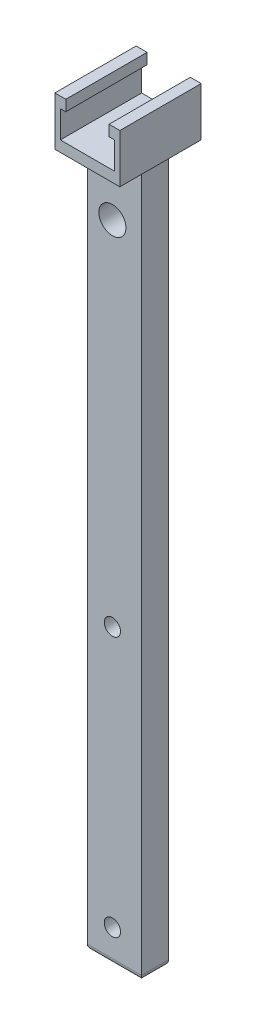
SolidWorks part; units mm, degrees
ref_plane "Front Plane" through (0, 0, 0) normal (0, 0, 1) x (1, 0, 0)
ref_plane "Top Plane" through (0, 0, 0) normal (0, 1, 0) x (1, 0, 0)
ref_plane "Right Plane" through (0, 0, 0) normal (1, 0, 0) x (0, 0, -1)
sketch "Sketch1" plane through (0, 0, 0) normal (0, 0, 1) x (1, 0, 0)
  line L0 (-5.6189, 9) -> (-5.6189, 0)
  line L1 (-5.6189, 0) -> (6.3811, 0)
  line L2 (6.3811, 0) -> (6.3811, 9)
  line L3 (4.3811, 9) -> (4.3811, 7)
  line L4 (4.3811, 7) -> (5.3991, 7)
  line L5 (5.3991, 7) -> (5.3991, 2)
  line L6 (5.3991, 2) -> (-4.6009, 2)
  line L7 (-4.6009, 2) -> (-4.6009, 7)
  line L8 (-4.6009, 7) -> (-3.6009, 7)
  line L9 (-3.6009, 7) -> (-3.6009, 9)
  line L10 (-3.6009, 9) -> (-5.6189, 9)
  line L11 (4.3811, 9) -> (6.3811, 9)
  point P5 (-4.6009, 4.5)
  dimension "D1" = 10
  dimension "D2" = 12
  dimension "D3" = 5
  dimension "D4" = 5
  dimension "D5" = 2
  dimension "D6" = 2
  dimension "D7" = 2
  dimension "D8" = 1.018
  dimension "D9" = 2
  dimension "D10" = 1
extrude "Boss-Extrude1" add sketch "Sketch1" along normal blind 15
sketch "Sketch2" plane through (0, 0, 0) normal (0, -1, 0) x (1, 0, 0)
  line L0 (-5.6189, 15) -> (6.3811, 0) construction
  line L1 (6.3811, 15) -> (-5.6189, 15)
  line L2 (6.3811, 15) -> (6.3811, 0)
  line L3 (6.3811, 0) -> (-5.6189, 0)
  line L4 (-5.6189, 15) -> (-5.6189, 0)
  line L5 (-5.6189, 0) -> (6.3811, 15) construction
  line L6 (0.3811, 7.5) -> (-5.6189, 7.5) construction
  line L8 (5.3811, 5) -> (-4.6189, 5)
  line L9 (5.3811, 5) -> (5.3811, 10)
  line L10 (5.3811, 10) -> (-4.6189, 10)
  line L11 (-4.6189, 5) -> (-4.6189, 10)
  line L12 (5.3811, 5) -> (-4.6189, 10) construction
  line L13 (5.3811, 10) -> (-4.6189, 5) construction
  dimension "D1" = 5
  dimension "D2" = 10
extrude "Boss-Extrude2" add sketch "Sketch2" along normal blind 130 contours L9 L8 L11 L10
fillet "Fillet3" radius 1 2 edges at (-4.6189, 0, 7.5) (0.3811, 0, 10)
fillet "Fillet4" radius 1 1 edges at (-0.1189, 0, 5)
fillet "Fillet5" radius 1 1 edges at (5.3811, 0, 7.5)
fillet "Fillet6" radius 1 4 edges at (-4.6189, -130, 7.5) (0.3811, -130, 5) (5.3811, -130, 7.5) (0.3811, -130, 10)
sketch "Sketch3" plane through (0, 0, 5) normal (0, 0, -1) x (-1, 0, 0)
  line L0 (4.6189, -1) -> (-5.3811, -1) construction
  line L1 (-5.3811, -129) -> (4.6189, -129) construction
  circle A0 centre (0, -11) radius 2.5
  circle A1 centre (0, -124) radius 1.5
  circle A2 centre (0, -76) radius 1.5
  dimension "D1" = 10
  dimension "D3" = 48
  dimension "D2" = 5
extrude "Cut-Extrude1" cut sketch "Sketch3" against normal up to next
